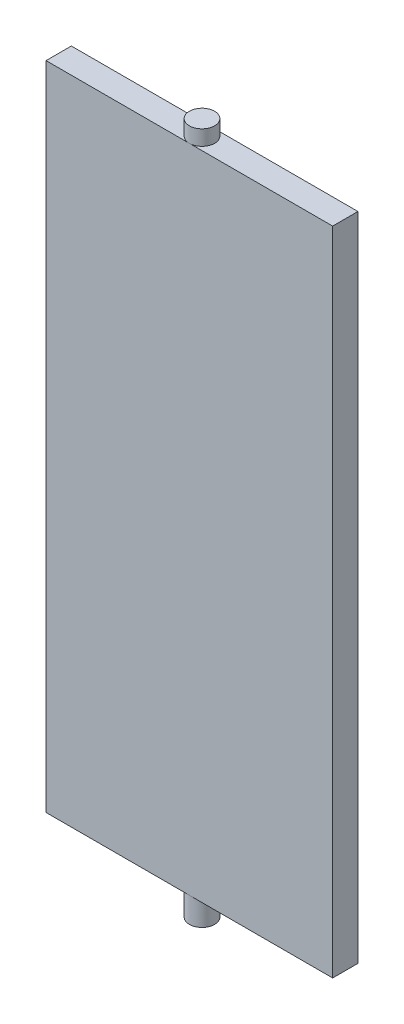
SolidWorks part; units mm, degrees
ref_plane "Front Plane" through (0, 0, 0) normal (1, 0, 0) x (0, 1, 0)
ref_plane "Top Plane" through (0, 0, 0) normal (0, 0, 1) x (0, 1, 0)
ref_plane "Right Plane" through (0, 0, 0) normal (0, 1, 0) x (-1, 0, 0)
sketch "Sketch1" plane through (0, 0, 0) normal (0, 0, 1) x (0, 1, 0)
  line L1 (0, 0) -> (77.25, 0)
  line L2 (0, 0) -> (0, 34)
  line L3 (0, 34) -> (77.25, 34)
  line L4 (77.25, 0) -> (77.25, 34)
  dimension "D1" = 77.25
  dimension "D2" = 34
extrude "Boss-Extrude1" add sketch "Sketch1" along normal blind 3
sketch "Sketch2" plane through (0, 77.25, 0) normal (0, 1, 0) x (-1, 0, 0)
  line L0 (17, 3) -> (17, 0)
  line L1 (0, 3) -> (34, 3) construction
  line L2 (0, 0) -> (34, 0) construction
  circle A0 centre (17, 1.5) radius 1.5
  dimension "D1" = 3
extrude "Boss-Extrude2" add sketch "Sketch2" along normal blind 1.8 contours L0 A0 | L0 A0 region at (-17.6366, 77.25, 1.5) region at (-16.3634, 77.25, 1.5)
extrude "Boss-Extrude3" add sketch "Sketch2<4>" against normal blind 3 from surface contours L0 A0 | L0 A0 region at (-17.6366, 77.25, 1.5) region at (-16.3634, 77.25, 1.5) starting at face at (-17, 0, 1.5)
sketch "Sketch2<4>" plane through (0, 77.25, 0) normal (0, 1, 0) x (-1, 0, 0) same geometry as "Sketch2"
